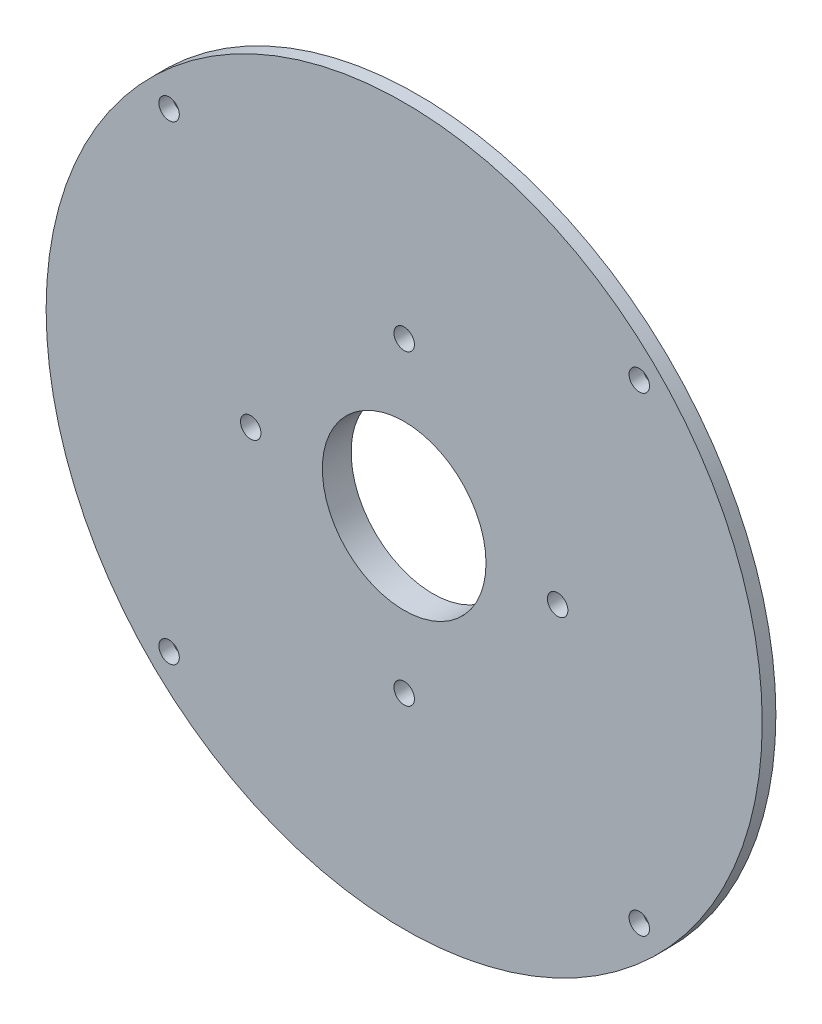
SolidWorks part; units mm, degrees
ref_plane "Front Plane" through (0, 0, 0) normal (0, 0, 1) x (1, 0, 0)
ref_plane "Top Plane" through (0, 0, 0) normal (0, 1, 0) x (1, 0, 0)
ref_plane "Right Plane" through (0, 0, 0) normal (1, 0, 0) x (0, 0, -1)
sketch "Sketch1" plane through (0, 0, 0) normal (0, 0, 1) x (1, 0, 0)
  circle A0 centre (0, 0) radius 30.625
  circle A1 centre (0, 0) radius 45
  circle A2 centre (0, 0) radius 52.5
  circle A3 centre (0, 0) radius 12
  dimension "D1" = 61.25
  dimension "D2" = 90
  dimension "D3" = 105
  dimension "D4" = 24
extrude "Boss-Extrude1" add sketch "Sketch1" against normal blind 4.22 contours A0 A3 region at (-29.7588, 0, 0)
extrude "Boss-Extrude2" add sketch "Sketch1<4>" against normal blind 2 contours A1 A0 | A2 A1 region at (-43.7272, 0, 0) region at (-51.0151, 0, 0)
sketch "Sketch1<4>" plane through (0, 0, 0) normal (0, 0, 1) x (1, 0, 0) same geometry as "Sketch1"
sketch "Sketch2" plane through (0, 0, 0) normal (0, 0, 1) x (1, 0, 0)
  circle A0 centre (0, 0) radius 48.75 construction
  circle A1 centre (-34.4715, 34.4715) radius 1.5
  circle A2 centre (34.4715, 34.4715) radius 1.5
  circle A3 centre (34.4715, -34.4715) radius 1.5
  circle A4 centre (-34.4715, -34.4715) radius 1.5
  circle A5 centre (0, 0) radius 22.5 construction
  circle A6 centre (0, 22.5) radius 1.5
  circle A7 centre (22.5, 0) radius 1.5
  circle A8 centre (0, -22.5) radius 1.5
  circle A9 centre (-22.5, 0) radius 1.5
  point P7 (-30.6891, 0)
  point P14 (0, 0)
  point P16 (0, 0)
  point P24 (0, 0)
  dimension "D1" = 97.5
  dimension "D2" = 3
  dimension "D4" = 45
  dimension "D5" = 3
  dimension "D3" = 4
  dimension "D6" = 4
extrude "Cut-Extrude1" cut sketch "Sketch2" against normal blind 20
